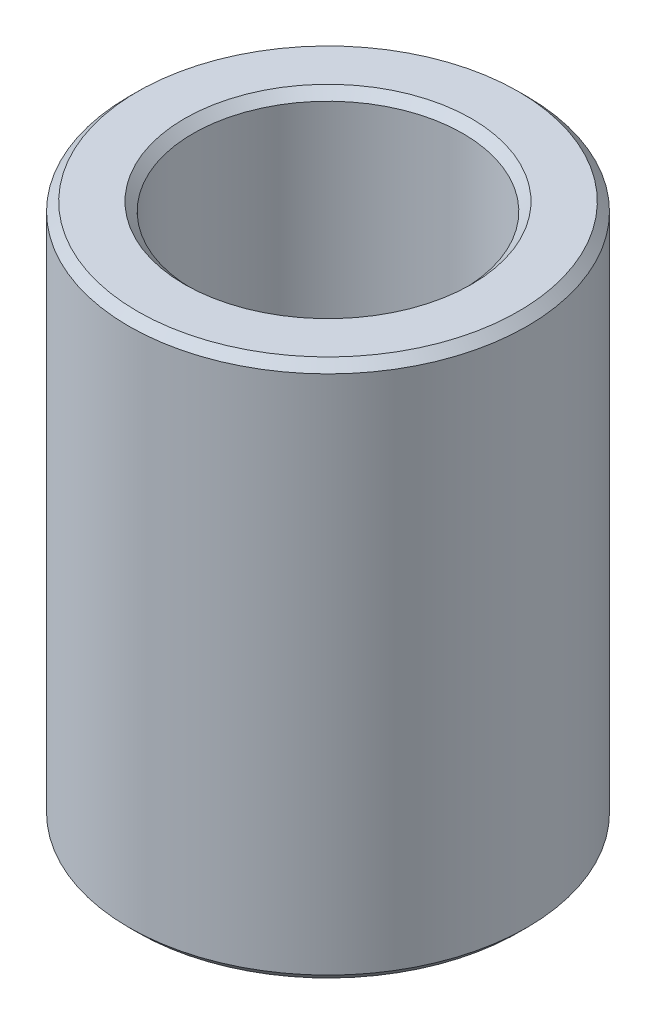
SolidWorks part; units mm, degrees
ref_plane "Front Plane" through (0, 0, 0) normal (0, 0, 1) x (1, 0, 0)
ref_plane "Top Plane" through (0, 0, 0) normal (0, 1, 0) x (1, 0, 0)
ref_plane "Right Plane" through (0, 0, 0) normal (1, 0, 0) x (0, 0, -1)
sketch "Sketch1" plane through (0, 0, 0) normal (0, 1, 0) x (1, 0, 0)
  circle A0 centre (0, 0) radius 60
  dimension "SLEEVE_OD" = 120
extrude "Boss-Extrude1" add sketch "Sketch1" along normal blind 162.1298
sketch "Sketch2" plane through (0, 0, 0) normal (0, 1, 0) x (1, 0, 0)
  circle A0 centre (0, 0) radius 40.682
  dimension "BORE_D" = 81.3639
extrude "Cut-Extrude1" cut sketch "Sketch2" along normal through all
chamfer "Chamfer1" distance 2.5912 angle 45 4 edges at (0, 162.1298, 40.682) (0, 0, 40.682) (0, 0, 60) (0, 162.1298, 60)
